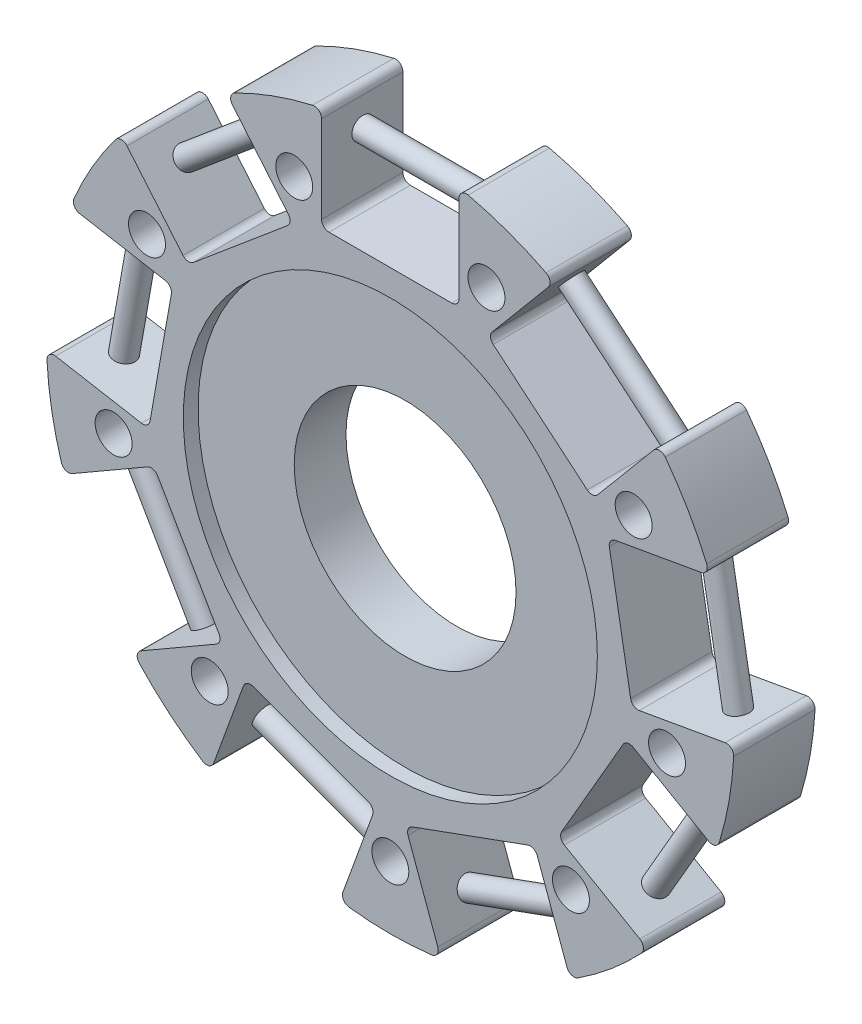
SolidWorks part; units mm, degrees
material "1060 Alloy"
ref_plane "Front Plane" through (0, 0, 0) normal (0, 0, 1) x (1, 0, 0)
ref_plane "Top Plane" through (0, 0, 0) normal (0, 1, 0) x (1, 0, 0)
ref_plane "Right Plane" through (0, 0, 0) normal (1, 0, 0) x (0, 0, -1)
sketch "Sketch1" plane through (0, 0, 0) normal (0, 0, 1) x (1, 0, 0)
  line L0 (0, 0) -> (0, 31.5376) construction
  line L3 (8.3, 31.5376) -> (-8.3, 31.5376)
  line L4 (-9.3, 32.5376) -> (-9.3, 44.3225)
  line L5 (26.6302, 18.8241) -> (13.9138, 29.4944)
  line L7 (13.7906, 30.9032) -> (21.3657, 39.9309)
  line L8 (-42.0342, 16.8552) -> (-30.4284, 14.8088)
  line L9 (35.6142, 27.9751) -> (28.039, 18.9473)
  line L10 (32.4998, -2.6975) -> (29.6172, 13.6504)
  line L11 (30.4284, 14.8088) -> (42.0342, 16.8552)
  line L13 (45.2641, -1.4622) -> (33.6582, -3.5086)
  line L14 (23.1624, -22.9568) -> (31.4624, -8.5808)
  line L15 (32.8284, -8.2148) -> (43.0344, -14.1072)
  line L16 (-43.0344, -14.1072) -> (-32.8284, -8.2148)
  line L18 (2.9871, -32.4744) -> (18.586, -26.7969)
  line L19 (19.8677, -27.3946) -> (23.8983, -38.4687)
  line L22 (-18.586, -26.7969) -> (-2.9871, -32.4744)
  line L23 (-2.3894, -33.7562) -> (-6.42, -44.8303)
  line L25 (-23.8983, -38.4687) -> (-19.8677, -27.3946)
  line L26 (-31.4624, -8.5808) -> (-23.1624, -22.9568)
  line L27 (-23.5284, -24.3229) -> (-33.7344, -30.2153)
  line L30 (-29.6172, 13.6504) -> (-32.4998, -2.6975)
  line L31 (-33.6582, -3.5086) -> (-45.2641, -1.4622)
  line L32 (33.7344, -30.2153) -> (23.5284, -24.3229)
  line L34 (-13.9138, 29.4944) -> (-26.6302, 18.8241)
  line L35 (-28.039, 18.9473) -> (-35.6142, 27.9751)
  line L37 (-21.3657, 39.9309) -> (-13.7906, 30.9032)
  line L48 (9.3, 44.3225) -> (9.3, 32.5376)
  line L49 (6.42, -44.8303) -> (2.3894, -33.7562)
  arc A0 (-21.0524, 41.4654) -> (-21.3657, 39.9309) centre (-20.5997, 40.5737) ccw
  arc A1 (-10.5264, 45.2965) -> (-21.0524, 41.4654) centre (0, 0) ccw
  arc A2 (-10.5264, 45.2965) -> (-9.3, 44.3225) centre (-10.3, 44.3225) cw
  arc A3 (-37.1797, 27.9329) -> (-35.6142, 27.9751) centre (-36.3802, 27.3323) cw
  arc A4 (-42.7805, 18.2321) -> (-42.0342, 16.8552) centre (-41.8605, 17.84) ccw
  arc A5 (-46.4363, -2.5008) -> (-45.2641, -1.4622) centre (-45.4377, -2.447) cw
  arc A6 (-44.4911, -13.5322) -> (-43.0344, -14.1072) centre (-43.5344, -13.2412) ccw
  arc A7 (-33.9648, -31.7644) -> (-33.7344, -30.2153) centre (-33.2344, -31.0813) cw
  arc A8 (-25.3839, -38.9646) -> (-23.8983, -38.4687) centre (-24.838, -38.1267) ccw
  arc A9 (5.6008, -46.165) -> (6.42, -44.8303) centre (5.4803, -45.1723) ccw
  arc A10 (-5.6008, -46.165) -> (-6.42, -44.8303) centre (-5.4803, -45.1723) cw
  arc A11 (33.9648, -31.7644) -> (33.7344, -30.2153) centre (33.2344, -31.0813) ccw
  arc A12 (25.3839, -38.9646) -> (23.8983, -38.4687) centre (24.838, -38.1267) cw
  arc A13 (-37.1797, 27.9329) -> (-42.7805, 18.2321) centre (0, 0) ccw
  arc A14 (44.4911, -13.5322) -> (43.0344, -14.1072) centre (43.5344, -13.2412) cw
  arc A15 (-46.4363, -2.5008) -> (-44.4911, -13.5322) centre (0, 0) ccw
  arc A16 (46.4363, -2.5008) -> (45.2641, -1.4622) centre (45.4377, -2.447) ccw
  arc A17 (-33.9648, -31.7644) -> (-25.3839, -38.9646) centre (0, 0) ccw
  arc A18 (42.0342, 16.8552) -> (42.7805, 18.2321) centre (41.8605, 17.84) ccw
  arc A19 (-5.6008, -46.165) -> (5.6008, -46.165) centre (0, 0) ccw
  arc A20 (37.1797, 27.9329) -> (35.6142, 27.9751) centre (36.3802, 27.3323) ccw
  arc A21 (25.3839, -38.9646) -> (33.9648, -31.7644) centre (0, 0) ccw
  arc A22 (44.4911, -13.5322) -> (46.4363, -2.5008) centre (0, 0) ccw
  arc A23 (21.0524, 41.4654) -> (21.3657, 39.9309) centre (20.5997, 40.5737) cw
  arc A24 (42.7805, 18.2321) -> (37.1797, 27.9329) centre (0, 0) ccw
  arc A25 (10.5264, 45.2965) -> (9.3, 44.3225) centre (10.3, 44.3225) ccw
  arc A26 (21.0524, 41.4654) -> (10.5264, 45.2965) centre (0, 0) ccw
  arc A27 (-23.1624, -22.9568) -> (-23.5284, -24.3229) centre (-24.0284, -23.4568) cw
  arc A28 (-18.586, -26.7969) -> (-19.8677, -27.3946) centre (-18.928, -27.7366) ccw
  arc A29 (-2.9871, -32.4744) -> (-2.3894, -33.7562) centre (-3.3291, -33.4141) cw
  arc A30 (2.9871, -32.4744) -> (2.3894, -33.7562) centre (3.3291, -33.4141) ccw
  arc A31 (18.586, -26.7969) -> (19.8677, -27.3946) centre (18.928, -27.7366) cw
  arc A32 (23.1624, -22.9568) -> (23.5284, -24.3229) centre (24.0284, -23.4568) ccw
  arc A33 (31.4624, -8.5808) -> (32.8284, -8.2148) centre (32.3284, -9.0808) cw
  arc A34 (32.4998, -2.6975) -> (33.6582, -3.5086) centre (33.4846, -2.5238) ccw
  arc A35 (29.6172, 13.6504) -> (30.4284, 14.8088) centre (30.602, 13.824) cw
  arc A36 (26.6302, 18.8241) -> (28.039, 18.9473) centre (27.273, 19.5901) ccw
  arc A37 (-32.4998, -2.6975) -> (-33.6582, -3.5086) centre (-33.4846, -2.5238) cw
  arc A38 (-31.4624, -8.5808) -> (-32.8284, -8.2148) centre (-32.3284, -9.0808) ccw
  arc A39 (13.9138, 29.4944) -> (13.7906, 30.9032) centre (14.5566, 30.2604) cw
  arc A40 (9.3, 32.5376) -> (8.3, 31.5376) centre (8.3, 32.5376) cw
  arc A41 (-8.3, 31.5376) -> (-9.3, 32.5376) centre (-8.3, 32.5376) cw
  arc A42 (-13.9138, 29.4944) -> (-13.7906, 30.9032) centre (-14.5566, 30.2604) ccw
  arc A43 (-26.6302, 18.8241) -> (-28.039, 18.9473) centre (-27.273, 19.5901) cw
  arc A44 (-29.6172, 13.6504) -> (-30.4284, 14.8088) centre (-30.602, 13.824) ccw
  point P22 (0, 0)
  point P66 (0, 0)
  dimension "D1" = 1
  dimension "D3" = 1
  dimension "D4" = 1
  dimension "D2" = 9
extrude "Boss-Extrude1" add sketch "Sketch1" along normal blind 11
sketch "Sketch3" plane through (0, 0, 11) normal (0, 0, 1) x (1, 0, 0)
  circle A0 centre (12.9968, 35.7083) radius 2.5
  circle A1 centre (-12.9968, 35.7083) radius 2.5
  circle A2 centre (32.909, 19) radius 2.5
  circle A3 centre (37.4227, -6.5986) radius 2.5
  circle A4 centre (24.4259, -29.1097) radius 2.5
  circle A5 centre (0, -38) radius 2.5
  circle A6 centre (-24.4259, -29.1097) radius 2.5
  circle A7 centre (-37.4227, -6.5986) radius 2.5
  circle A8 centre (-32.909, 19) radius 2.5
  point P25 (0, 0)
  dimension "D1" = 9
  dimension "D2" = 5
extrude "Cut-Extrude4" cut sketch "Sketch3" against normal blind 11
sketch "Sketch7" plane through (0, 0, 11) normal (0, 0, 1) x (1, 0, 0)
  circle A0 centre (0, 0) radius 28
extrude "Cut-Extrude5" cut sketch "Sketch7" against normal blind 2
sketch "Sketch10" plane through (0, 0, 0) normal (0, 0, -1) x (-1, 0, 0)
  circle A0 centre (0, 0) radius 28
extrude "Cut-Extrude6" cut sketch "Sketch10" against normal blind 2
sketch "Sketch12" plane through (0, 0, 2) normal (0, 0, -1) x (-1, 0, 0)
  circle A0 centre (0, 0) radius 15
extrude "Cut-Extrude7" cut sketch "Sketch12" against normal through all
sketch "Sketch13" plane through (7.1242, -5.9779, 0) normal (-0.766, 0.6428, 0) x (0, 0, 1)
  line L0 (11, 32.5376) -> (0, 32.5376) construction
  circle A0 centre (5.5, 40.5376) radius 1.5
  dimension "D1" = 8
extrude "Boss-Extrude2" add sketch "Sketch13" along normal blind 18.5
pattern_circular "CirPattern1" count 9 over 360 about axis through (0, 0, 0) along (0, 0, -1) of "Boss-Extrude2"
sketch "Sketch15" plane through (0, 0, 2) normal (0, 0, -1) x (-1, 0, 0)
  line L0 (0, 0) -> (0, 50)
  dimension "D1" = 50
sketch "Sketch16" plane through (0, 0, 0) normal (0, 0, -1) x (-1, 0, 0)
  circle A0 centre (0, 0) radius 49.8472
  dimension "D1" = 99.6945
